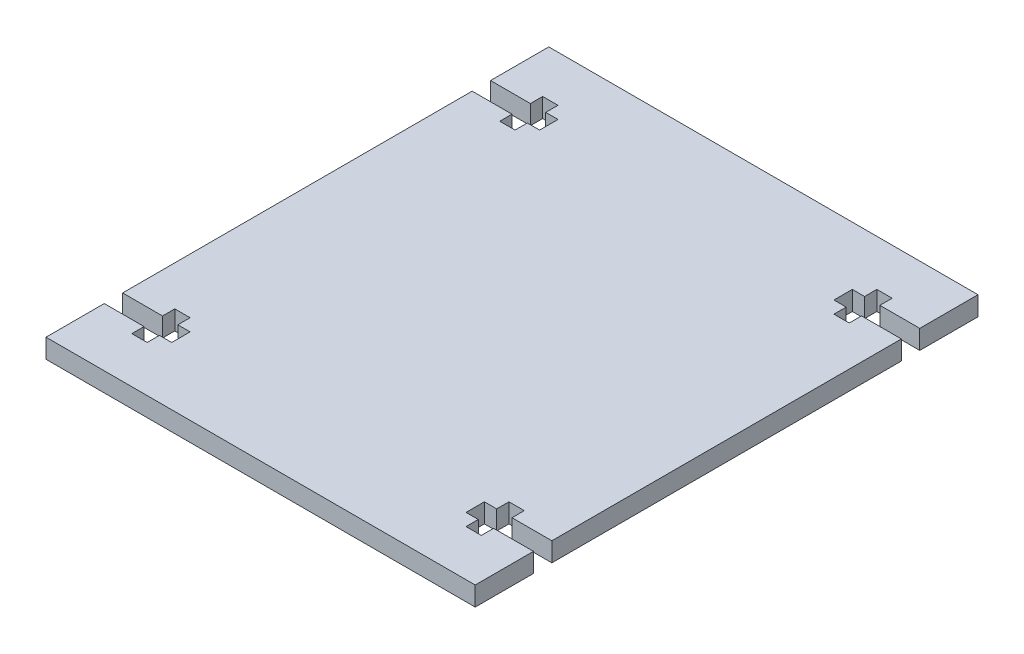
SolidWorks part; units mm, degrees
ref_plane "Front Plane" through (0, 0, 0) normal (0, 0, 1) x (1, 0, 0)
ref_plane "Top Plane" through (0, 0, 0) normal (0, 1, 0) x (1, 0, 0)
ref_plane "Right Plane" through (0, 0, 0) normal (1, 0, 0) x (0, 0, -1)
sketch "Sketch1" plane through (0, 0, 0) normal (0, 1, 0) x (1, 0, 0)
  line L0 (0, 30) -> (35, 30) construction
  line L1 (0, 41) -> (35, 41)
  line L2 (0, 41) -> (0, 0)
  line L3 (0, 0) -> (35, 0)
  line L4 (35, 41) -> (35, 31.5)
  line L5 (35, 31.5) -> (28.5, 31.5)
  line L6 (28.5, 31.5) -> (28.5, 33.5)
  line L7 (28.5, 33.5) -> (26, 33.5)
  line L8 (26, 33.5) -> (26, 31.5)
  line L9 (26, 31.5) -> (24, 31.5)
  line L10 (24, 31.5) -> (24, 28.5)
  line L11 (24, 28.5) -> (26, 28.5)
  line L12 (26, 28.5) -> (26, 26.5)
  line L13 (26, 26.5) -> (28.5, 26.5)
  line L14 (28.5, 26.5) -> (28.5, 28.5)
  line L15 (28.5, 28.5) -> (35, 28.5)
  line L16 (35, 28.5) -> (35, 0)
  point P17 (24, 30)
  point P20 (29.4085, 19.3874)
  point P21 (28.5, 22.219)
  dimension "D1" = 35
  dimension "D2" = 2.5
  dimension "D3" = 9
  dimension "D4" = 2
  dimension "D5" = 3
  dimension "D6" = 7.5
  dimension "D7" = 7
  dimension "D8" = 30
extrude "Boss-Extrude1" add sketch "Sketch1" along normal mid plane 3.125
mirror "Mirror1" about plane through (0, 0, 0) normal (1, 0, 0) of "Boss-Extrude1"
mirror "Mirror4" about plane through (0, 0, 0) normal (0, 0, 1) of "Mirror1"
